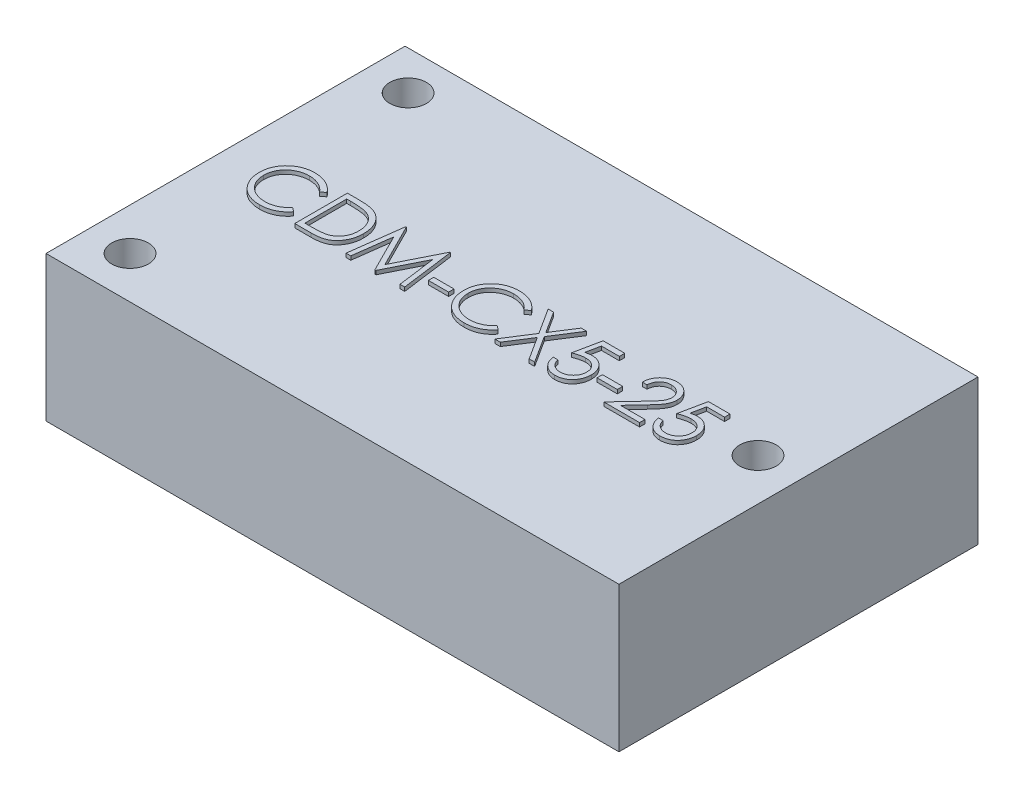
SolidWorks part; units mm, degrees
ref_plane "Front Plane" through (0, 0, 0) normal (0, 0, 1) x (1, 0, 0)
ref_plane "Top Plane" through (0, 0, 0) normal (0, 1, 0) x (1, 0, 0)
ref_plane "Right Plane" through (0, 0, 0) normal (1, 0, 0) x (0, 0, -1)
sketch "Sketch1" plane through (0, 0, 0) normal (0, 1, 0) x (1, 0, 0)
  line L1 (-19.05, 11.938) -> (19.05, 11.938)
  line L2 (-19.05, 11.938) -> (-19.05, -11.938)
  line L3 (-19.05, -11.938) -> (19.05, -11.938)
  line L4 (19.05, 11.938) -> (19.05, -11.938)
  line L5 (-19.05, 11.938) -> (19.05, -11.938) construction
  line L6 (-19.05, -11.938) -> (19.05, 11.938) construction
  circle A0 centre (-16.256, 9.3472) radius 1.2192
  circle A1 centre (-16.256, -9.144) radius 1.2192
  circle A2 centre (16.256, 0.1016) radius 1.2192
  point P0 (0, 0)
  dimension "D3" = 2.4384
  dimension "D4" = 2.4384
  dimension "D5" = 2.4384
  dimension "D1" = 38.1
  dimension "D2" = 23.876
  dimension "D6" = 18.4912
  dimension "D7" = 2.794
  dimension "D8" = 2.794
  dimension "D9" = 32.512
  dimension "D10" = 12.0396
  dimension "D11" = 2.794
extrude "Boss-Extrude1" add sketch "Sketch1" against normal blind 9.652
sketch "Sketch2" plane through (0, 0, 0) normal (0, 1, 0) x (1, 0, 0)
  text T0 "CDM-CX5-25"
extrude "Boss-Extrude2" add sketch "Sketch2" along normal blind 0.254
